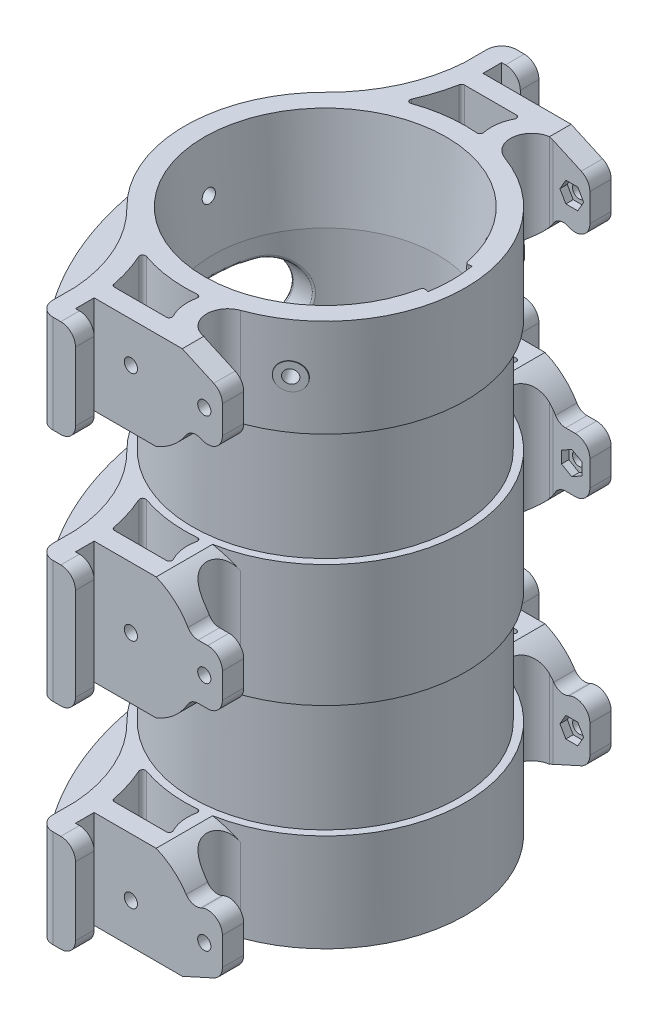
SolidWorks part; units mm, degrees
ref_plane "Front Plane" through (0, 0, 0) normal (0, 0, 1) x (1, 0, 0)
ref_plane "Top Plane" through (0, 0, 0) normal (0, 1, 0) x (1, 0, 0)
ref_plane "Right Plane" through (0, 0, 0) normal (1, 0, 0) x (0, 0, -1)
sketch "Sketch1" plane through (0, 0, 0) normal (0, 1, 0) x (1, 0, 0)
  line L0 (0, 38.25) -> (0, 45.25) construction
  circle A0 centre (0, 0) radius 38.25
  circle A1 centre (0, 0) radius 45.25
  dimension "D1" = 76.5
  dimension "D2" = 7
extrude "Boss-Extrude1" add sketch "Sketch1" along normal mid plane 185
sketch "Sketch2" plane through (0, -92.5, 0) normal (0, -1, 0) x (1, 0, 0)
  line L0 (0, 36.25) -> (0, 38.25) construction
  circle A0 centre (0, 0) radius 36.25
  circle A1 centre (0, 0) radius 38.25 construction
  circle A2 centre (0, 0) radius 38.25
  dimension "D1" = 2
extrude "Boss-Extrude2" add sketch "Sketch2" against normal blind 100 from offset 6.35 offset against normal yes
sketch "Sketch7" plane through (0, 0, 0) normal (1, 0, 0) x (0, 0, -1)
  line L0 (45.25, 92.5) -> (-45.25, 92.5) construction
  line L1 (12.5, 40) -> (-12.5, 40) construction
  line L2 (12.5, 27.5) -> (-12.5, 27.5)
  line L3 (12.5, 52.5) -> (-12.5, 52.5)
  circle A0 centre (0, 40) radius 12.5 construction
  arc A1 (12.5, 27.5) -> (12.5, 52.5) centre (12.5, 40) ccw
  arc A2 (-12.5, 52.5) -> (-12.5, 27.5) centre (-12.5, 40) ccw
  point P7 (0, 40)
  dimension "D2" = 25
  dimension "D3" = 25
  dimension "D1" = 52.5
extrude "Cut-Extrude4" cut sketch "Sketch7" against normal through all
sketch "Sketch8" plane through (0, 0, 0) normal (0, 1, 0) x (1, 0, 0)
  line L1 (17.5, -66.175) -> (128.1882, -66.175) construction
  line L2 (-18.85, -66.175) -> (-18.85, -78.875)
  line L3 (-18.85, -78.875) -> (-6.15, -78.875)
  line L4 (45.25, 0) -> (-45.25, 0) construction
  line L5 (31.75, 0) -> (50, 0) construction
  line L6 (-6.15, -78.875) -> (-6.15, -72.525)
  line L7 (-12.5, -72.525) -> (17.5, -72.525) construction
  line L8 (-6.15, -72.525) -> (-12.5, -72.525)
  line L9 (-12.5, -72.525) -> (-12.5, -66.175)
  line L10 (-12.5, -66.175) -> (43.65, -66.175)
  line L11 (-12.5, 66.175) -> (43.65, 66.175)
  line L12 (-12.5, 72.525) -> (-12.5, 66.175)
  line L13 (-6.15, 72.525) -> (-12.5, 72.525)
  line L14 (-6.15, 78.875) -> (-6.15, 72.525)
  line L15 (-18.85, 78.875) -> (-6.15, 78.875)
  line L16 (-18.85, 66.175) -> (-18.85, 78.875)
  line L18 (43.65, -66.175) -> (43.65, -58.9107)
  line L19 (43.65, -58.9107) -> (18.65, -58.9107)
  line L20 (43.65, 58.9107) -> (18.65, 58.9107)
  line L21 (43.65, 66.175) -> (43.65, 58.9107)
  line L22 (-12.5, -72.525) -> (-18.85, -72.525) construction
  arc A0 (-32.8241, -31.1471) -> (-18.85, -66.175) centre (-69.7381, -66.175) cw
  circle A1 centre (0, 0) radius 45.25 construction
  arc A2 (-32.8241, -31.1471) -> (15.7007, -42.4388) centre (0, 0) ccw
  arc A3 (-32.8241, 31.1471) -> (15.7007, 42.4388) centre (0, 0) cw
  arc A4 (-32.8241, 31.1471) -> (-18.85, 66.175) centre (-69.7381, 66.175) ccw
  arc A9 (18.65, -58.9107) -> (15.7007, -42.4388) centre (18.65, -50.4107) cw
  arc A10 (18.65, 58.9107) -> (15.7007, 42.4388) centre (18.65, 50.4107) ccw
  dimension "D1" = 8.5
  dimension "D2" = 62.5
  dimension "D3" = 25
extrude "Boss-Extrude3" add sketch "Sketch8" along normal up to surface and the other way up to surface up to face at (0, 92.5, 45.25) other way up to face at (0, -92.5, 45.25)
sketch "Sketch10" plane through (0, 0, 66.175) normal (0, 0, 1) x (1, 0, 0)
  line L0 (17.5, -92.5) -> (43.65, -92.5)
  line L1 (43.65, -92.5) -> (43.65, -80.6536)
  line L2 (-6.15, -59.2129) -> (-32.8241, -59.2129)
  line L3 (128.1882, -42.3564) -> (17.5, -92.5) construction
  line L4 (43.65, -80.6536) -> (17.5, -92.5)
  line L5 (43.65, 80.6536) -> (43.65, 92.5)
  line L6 (17.5, 92.5) -> (128.1882, 42.3564) construction
  line L7 (43.65, 92.5) -> (17.5, 92.5)
  line L8 (-12.5, 92.5) -> (43.65, 92.5) construction
  line L9 (17.5, 92.5) -> (43.65, 80.6536)
  line L10 (43.65, -60.1882) -> (43.65, -9.3209)
  line L11 (79.953, -43.7423) -> (23.8431, -69.161) construction
  line L12 (22.9086, -9.3209) -> (60.2886, -9.3209) construction
  line L21 (22.9086, -9.3209) -> (43.65, -9.3209)
  line L23 (43.65, -60.1882) -> (23.8431, -69.161)
  line L25 (-6.15, 92.5) -> (-6.15, -92.5) construction
  line L26 (-32.8241, 92.5) -> (-32.8241, -92.5) construction
  line L32 (-32.8241, -59.2129) -> (-32.8241, -20.7871)
  line L36 (-32.8241, -20.7871) -> (-6.15, -20.7871)
  line L40 (0, 0) -> (-32.8241, 0) construction
  line L45 (8.611, -59.2129) -> (-6.15, -59.2129)
  line L46 (8.611, -20.7871) -> (-6.15, -20.7871)
  line L47 (-32.8241, 59.2129) -> (-32.8241, 20.7871)
  line L48 (-6.15, 59.2129) -> (-32.8241, 59.2129)
  line L49 (8.611, 59.2129) -> (-6.15, 59.2129)
  line L50 (43.65, 60.1882) -> (23.8431, 69.161)
  line L51 (43.65, 60.1882) -> (43.65, 9.3209)
  line L52 (22.9086, 9.3209) -> (43.65, 9.3209)
  line L53 (8.611, 20.7871) -> (-6.15, 20.7871)
  line L54 (-32.8241, 20.7871) -> (-6.15, 20.7871)
  line L55 (43.65, 92.5) -> (43.65, -92.5) construction
  arc A6 (18.8427, -67.7035) -> (23.8431, -69.161) centre (22.1925, -65.5175) ccw construction
  arc A7 (18.8427, -67.7035) -> (8.611, -59.2129) centre (0, -80) ccw construction
  arc A10 (8.611, -20.7871) -> (19.4507, -11.3102) centre (0, 0) ccw construction
  arc A11 (22.9086, -9.3209) -> (19.4507, -11.3102) centre (22.9086, -13.3209) ccw construction
  arc A18 (18.8427, -67.7035) -> (23.8431, -69.161) centre (22.1925, -65.5175) ccw
  arc A19 (18.8427, -67.7035) -> (8.611, -59.2129) centre (0, -80) ccw
  arc A22 (8.611, -20.7871) -> (19.4507, -11.3102) centre (0, 0) ccw
  arc A23 (22.9086, -9.3209) -> (19.4507, -11.3102) centre (22.9086, -13.3209) ccw
  arc A24 (18.8427, 67.7035) -> (8.611, 59.2129) centre (0, 80) cw
  arc A25 (18.8427, 67.7035) -> (23.8431, 69.161) centre (22.1925, 65.5175) cw
  arc A26 (22.9086, 9.3209) -> (19.4507, 11.3102) centre (22.9086, 13.3209) cw
  arc A27 (8.611, 20.7871) -> (19.4507, 11.3102) centre (0, 0) cw
extrude "Cut-Extrude6" cut sketch "Sketch10" against normal up to surface and the other way through all up to face at (-41.5057, 40, 0)
sketch "Sketch11" plane through (0, 0, -78.875) normal (0, 0, -1) x (-1, 0, 0)
  line L3 (-43.65, 92.5) -> (-43.65, 80.6536)
  line L4 (-17.5, 92.5) -> (-43.65, 92.5)
  line L5 (-43.65, 80.6536) -> (-17.5, 92.5)
  line L6 (-43.65, 92.5) -> (-43.65, 80.6536)
  line L7 (-17.5, 92.5) -> (-43.65, 92.5)
  line L8 (-43.65, 80.6536) -> (-17.5, 92.5)
  line L9 (-43.65, -92.5) -> (-17.5, -92.5)
  line L10 (-43.65, -80.6536) -> (-43.65, -92.5)
  line L11 (-17.5, -92.5) -> (-43.65, -80.6536)
  line L12 (-43.65, -92.5) -> (-17.5, -92.5)
  line L13 (-43.65, -80.6536) -> (-43.65, -92.5)
  line L14 (-17.5, -92.5) -> (-43.65, -80.6536)
  line L20 (32.8241, 20.7871) -> (32.8241, 59.2129)
  line L21 (6.15, 20.7871) -> (32.8241, 20.7871)
  line L22 (-8.611, 20.7871) -> (6.15, 20.7871)
  line L23 (-43.65, 9.3209) -> (-22.9086, 9.3209)
  line L24 (-43.65, 60.1882) -> (-43.65, 9.3209)
  line L25 (-23.8431, 69.161) -> (-43.65, 60.1882)
  line L26 (6.15, 59.2129) -> (-8.611, 59.2129)
  line L27 (32.8241, 59.2129) -> (6.15, 59.2129)
  line L28 (32.8241, 20.7871) -> (32.8241, 59.2129)
  line L29 (6.15, 20.7871) -> (32.8241, 20.7871)
  line L30 (-8.611, 20.7871) -> (6.15, 20.7871)
  line L31 (-43.65, 9.3209) -> (-22.9086, 9.3209)
  line L32 (-43.65, 60.1882) -> (-43.65, 9.3209)
  line L33 (-23.8431, 69.161) -> (-43.65, 60.1882)
  line L34 (6.15, 59.2129) -> (-8.611, 59.2129)
  line L35 (32.8241, 59.2129) -> (6.15, 59.2129)
  line L36 (-22.9086, -9.3209) -> (-43.65, -9.3209)
  line L37 (-43.65, -9.3209) -> (-43.65, -60.1882)
  line L38 (-43.65, -60.1882) -> (-23.8431, -69.161)
  line L39 (-8.611, -59.2129) -> (6.15, -59.2129)
  line L40 (6.15, -59.2129) -> (32.8241, -59.2129)
  line L41 (32.8241, -59.2129) -> (32.8241, -20.7871)
  line L42 (32.8241, -20.7871) -> (6.15, -20.7871)
  line L43 (6.15, -20.7871) -> (-8.611, -20.7871)
  line L44 (-22.9086, -9.3209) -> (-43.65, -9.3209)
  line L45 (-43.65, -9.3209) -> (-43.65, -60.1882)
  line L46 (-43.65, -60.1882) -> (-23.8431, -69.161)
  line L47 (-8.611, -59.2129) -> (6.15, -59.2129)
  line L48 (6.15, -59.2129) -> (32.8241, -59.2129)
  line L49 (32.8241, -59.2129) -> (32.8241, -20.7871)
  line L50 (32.8241, -20.7871) -> (6.15, -20.7871)
  line L51 (6.15, -20.7871) -> (-8.611, -20.7871)
  arc A4 (-8.611, 20.7871) -> (-19.4507, 11.3102) centre (0, 0) ccw
  arc A5 (-22.9086, 9.3209) -> (-19.4507, 11.3102) centre (-22.9086, 13.3209) ccw
  arc A6 (-18.8427, 67.7035) -> (-23.8431, 69.161) centre (-22.1925, 65.5175) ccw
  arc A7 (-18.8427, 67.7035) -> (-8.611, 59.2129) centre (0, 80) ccw
  arc A8 (-8.611, 20.7871) -> (-19.4507, 11.3102) centre (0, 0) ccw
  arc A9 (-22.9086, 9.3209) -> (-19.4507, 11.3102) centre (-22.9086, 13.3209) ccw
  arc A10 (-18.8427, 67.7035) -> (-23.8431, 69.161) centre (-22.1925, 65.5175) ccw
  arc A11 (-18.8427, 67.7035) -> (-8.611, 59.2129) centre (0, 80) ccw
  arc A12 (-23.8431, -69.161) -> (-18.8427, -67.7035) centre (-22.1925, -65.5175) ccw
  arc A13 (-8.611, -59.2129) -> (-18.8427, -67.7035) centre (0, -80) ccw
  arc A14 (-19.4507, -11.3102) -> (-8.611, -20.7871) centre (0, 0) ccw
  arc A15 (-19.4507, -11.3102) -> (-22.9086, -9.3209) centre (-22.9086, -13.3209) ccw
  arc A16 (-23.8431, -69.161) -> (-18.8427, -67.7035) centre (-22.1925, -65.5175) ccw
  arc A17 (-8.611, -59.2129) -> (-18.8427, -67.7035) centre (0, -80) ccw
  arc A18 (-19.4507, -11.3102) -> (-8.611, -20.7871) centre (0, 0) ccw
  arc A19 (-19.4507, -11.3102) -> (-22.9086, -9.3209) centre (-22.9086, -13.3209) ccw
  dimension "D1" = 0
  dimension "D2" = 0
  dimension "D3" = 0
  dimension "D4" = 0
extrude "Cut-Extrude7" cut sketch "Sketch11" against normal up to surface (66.9486 mm away) up to face at (-3.9052, 0.3336, 17.6166)
fillet "Fillet5" radius 5 6 edges at (-18.85, -75.8565, -78.875) (-18.85, 0, -78.875) (-18.85, 75.8565, -78.875) (-18.85, 0, 78.875) (-18.85, -75.8565, 78.875) (-18.85, 75.8565, 78.875)
sketch "Sketch14" plane through (0, 0, -66.175) normal (0, 0, -1) x (-1, 0, 0)
  line L0 (0, 0) -> (-25, 0) construction
  line L5 (-25, 78.8696) -> (-25, 0) construction
  circle A3 centre (-25, 78.8696) radius 2.25
  circle A5 centre (-25, 0) radius 2.25
  circle A7 centre (-25, -78.8696) radius 2.25
  circle A8 centre (0, 0) radius 2.25
  circle A9 centre (0, 78.8696) radius 2.25
  circle A10 centre (0, -78.8696) radius 2.25
  dimension "D1" = 25
  dimension "D2" = 78.8696
  dimension "D3" = 4.5
extrude "Cut-Extrude8" cut sketch "Sketch14" against normal up to surface (7.2643 mm away) up to face at (27.8361, -73.0039, -58.9107)
sketch "Sketch15" plane through (0, 0, 66.175) normal (0, 0, 1) x (1, 0, 0)
  circle A1 centre (0, -78.8696) radius 2.25
  circle A3 centre (0, -78.8696) radius 2.25
  circle A5 centre (0, 78.8696) radius 2.25
  circle A7 centre (0, 78.8696) radius 2.25
  circle A9 centre (0, 0) radius 2.25
  circle A11 centre (0, 0) radius 2.25
  circle A13 centre (25, 78.8696) radius 2.25
  circle A14 centre (25, 78.8696) radius 2.25
  circle A15 centre (25, -78.8696) radius 2.25
  circle A16 centre (25, -78.8696) radius 2.25
  circle A17 centre (25, 0) radius 2.25
  circle A18 centre (25, 0) radius 2.25
  dimension "D1" = 0
  dimension "D2" = 0
  dimension "D3" = 0
  dimension "D4" = 0
  dimension "D5" = 0
  dimension "D6" = 0
extrude "Cut-Extrude9" cut sketch "Sketch15" against normal up to surface (7.2643 mm away) up to face at (27.8361, -73.0039, 58.9107)
sketch "Sketch16" plane through (0, 92.5, 0) normal (0, 1, 0) x (1, 0, 0)
  line L0 (-45.25, 0) -> (-47.75, 0) construction
  circle A0 centre (0, 0) radius 47.75
  circle A1 centre (0, 0) radius 45.25
  arc A2 (-32.8241, 31.1471) -> (-32.8241, -31.1471) centre (0, 0) ccw construction
  dimension "D1" = 2.5
extrude "Boss-Extrude4" add sketch "Sketch16" against normal up to surface (33.2871 mm away) up to face at (-10.3824, 59.2129, 65.577)
sketch "Sketch17" plane through (0, -92.5, 0) normal (0, -1, 0) x (1, 0, 0)
  circle A1 centre (0, 0) radius 45.25
  circle A2 centre (0, 0) radius 45.25
  circle A3 centre (0, 0) radius 47.75
  circle A4 centre (0, 0) radius 47.75
  dimension "D1" = 0
  dimension "D2" = 0
extrude "Boss-Extrude5" add sketch "Sketch17" against normal up to surface (33.2871 mm away) up to face at (-10.3824, -59.2129, 65.577)
sketch "Sketch18" plane through (0, -20.7871, 0) normal (0, -1, 0) x (1, 0, 0)
  circle A1 centre (0, 0) radius 47.75
  circle A2 centre (0, 0) radius 47.75
  circle A3 centre (0, 0) radius 45.25
  circle A4 centre (0, 0) radius 45.25
  dimension "D1" = 0
  dimension "D2" = 0
extrude "Boss-Extrude6" add sketch "Sketch18" against normal up to surface (41.5741 mm away) up to face at (-10.3824, 20.7871, 65.577)
sketch "Sketch20" plane through (0, 0, 0) normal (1, 0, 0) x (0, 0, -1)
  line L0 (-45.25, -20.7871) -> (45.25, -20.7871) construction
  line L1 (46.9672, -59.2129) -> (-46.9672, -59.2129) construction
  line L2 (-45.25, 59.2129) -> (45.25, 59.2129) construction
  line L3 (46.9672, 20.7871) -> (-46.9672, 20.7871) construction
  line L4 (-45.25, -20.7871) -> (45.25, -20.7871) construction
  line L5 (46.9672, -59.2129) -> (-46.9672, -59.2129) construction
  line L6 (-45.25, 59.2129) -> (45.25, 59.2129) construction
  line L7 (46.9672, 20.7871) -> (-46.9672, 20.7871) construction
  line L8 (0, -20.7871) -> (0, -59.2129) construction
  line L9 (0, 59.2129) -> (0, 20.7871) construction
  line L10 (-10, 40) -> (10, 40) construction
  line L11 (-10, 45) -> (10, 45)
  line L12 (-10, 35) -> (10, 35)
  line L13 (0, 0) -> (46.4328, 0) construction
  line L14 (46.4328, 19.5496) -> (46.4328, -19.5496) construction
  line L15 (-10, -40) -> (10, -40) construction
  line L16 (-10, -45) -> (10, -45)
  line L17 (-10, -35) -> (10, -35)
  arc A2 (-10, 45) -> (-10, 35) centre (-10, 40) ccw
  arc A3 (10, 35) -> (10, 45) centre (10, 40) ccw
  arc A4 (-10, -45) -> (-10, -35) centre (-10, -40) cw
  arc A5 (10, -35) -> (10, -45) centre (10, -40) cw
  point P2 (0, 40)
  point P14 (0, -20.7871)
  point P30 (0, -40)
  dimension "D1" = 20
  dimension "D2" = 5
extrude "Cut-Extrude10" [suppressed] cut sketch "Sketch20" along normal through all
pattern_circular "CirPattern1" [suppressed] count 6 over 360 reverse direction yes of bodies 118
ref_plane "Plane1" through (-26.1107, -92.5, 39.9787) normal (0, -1, 0) x (-1, 0, 0)
sketch "Sketch23" plane through (0, -92.5, 0) normal (0, -1, 0) x (1, 0, 0)
  line L0 (0, 0) -> (-47.75, 0) construction
  arc A0 (-18.85, 66.175) -> (-33.5786, 33.9491) centre (-68.7395, 69.4978) cw
  arc A1 (-26.1107, 39.9787) -> (-26.1107, -39.9787) centre (0, 0) ccw construction
  arc A2 (-33.5786, 33.9491) -> (-26.1107, 39.9787) centre (0, 0) cw
  arc A3 (-18.85, 66.175) -> (-26.1107, 39.9787) centre (-69.7381, 66.175) cw
  arc A4 (-18.85, -66.175) -> (-26.1107, -39.9787) centre (-69.7381, -66.175) ccw
  arc A5 (-33.5786, -33.9491) -> (-26.1107, -39.9787) centre (0, 0) ccw
  arc A6 (-18.85, -66.175) -> (-33.5786, -33.9491) centre (-68.7395, -69.4978) ccw
  arc A7 (-26.1107, 39.9787) -> (-18.85, 66.175) centre (-69.7381, 66.175) ccw construction
  dimension "D1" = 50
extrude "Boss-Extrude7" add sketch "Sketch23" against normal up to surface (33.2871 mm away) up to face at (-8.8243, -59.2129, 0)
sketch "Sketch24" plane through (0, 92.5, 0) normal (0, 1, 0) x (1, 0, 0)
  arc A3 (-26.1107, 39.9787) -> (-18.85, 66.175) centre (-69.7381, 66.175) ccw
  arc A4 (-26.1107, 39.9787) -> (-33.5786, 33.9491) centre (0, 0) ccw
  arc A5 (-33.5786, 33.9491) -> (-18.85, 66.175) centre (-68.7395, 69.4978) ccw
  arc A6 (-26.1107, 39.9787) -> (-18.85, 66.175) centre (-69.7381, 66.175) ccw
  arc A7 (-26.1107, 39.9787) -> (-33.5786, 33.9491) centre (0, 0) ccw
  arc A8 (-33.5786, 33.9491) -> (-18.85, 66.175) centre (-68.7395, 69.4978) ccw
  arc A9 (-18.85, -66.175) -> (-33.5786, -33.9491) centre (-68.7395, -69.4978) ccw
  arc A10 (-33.5786, -33.9491) -> (-26.1107, -39.9787) centre (0, 0) ccw
  arc A11 (-18.85, -66.175) -> (-26.1107, -39.9787) centre (-69.7381, -66.175) ccw
  arc A12 (-18.85, -66.175) -> (-33.5786, -33.9491) centre (-68.7395, -69.4978) ccw
  arc A13 (-33.5786, -33.9491) -> (-26.1107, -39.9787) centre (0, 0) ccw
  arc A14 (-18.85, -66.175) -> (-26.1107, -39.9787) centre (-69.7381, -66.175) ccw
  dimension "D1" = 0
  dimension "D2" = 0
extrude "Boss-Extrude8" add sketch "Sketch24" against normal up to surface (33.2871 mm away) up to face at (-45.25, 59.2129, 0)
sketch "Sketch25" plane through (0, 20.7871, 0) normal (0, 1, 0) x (1, 0, 0)
  arc A3 (-18.85, -66.175) -> (-33.5786, -33.9491) centre (-68.7395, -69.4978) ccw
  arc A4 (-33.5786, -33.9491) -> (-26.1107, -39.9787) centre (0, 0) ccw
  arc A5 (-18.85, -66.175) -> (-26.1107, -39.9787) centre (-69.7381, -66.175) ccw
  arc A6 (-18.85, -66.175) -> (-33.5786, -33.9491) centre (-68.7395, -69.4978) ccw
  arc A7 (-33.5786, -33.9491) -> (-26.1107, -39.9787) centre (0, 0) ccw
  arc A8 (-18.85, -66.175) -> (-26.1107, -39.9787) centre (-69.7381, -66.175) ccw
  arc A9 (-26.1107, 39.9787) -> (-18.85, 66.175) centre (-69.7381, 66.175) ccw
  arc A10 (-33.5786, 33.9491) -> (-18.85, 66.175) centre (-68.7395, 69.4978) ccw
  arc A11 (-26.1107, 39.9787) -> (-33.5786, 33.9491) centre (0, 0) ccw
  arc A12 (-26.1107, 39.9787) -> (-18.85, 66.175) centre (-69.7381, 66.175) ccw
  arc A13 (-33.5786, 33.9491) -> (-18.85, 66.175) centre (-68.7395, 69.4978) ccw
  arc A14 (-26.1107, 39.9787) -> (-33.5786, 33.9491) centre (0, 0) ccw
  dimension "D1" = 0
  dimension "D2" = 0
extrude "Boss-Extrude9" add sketch "Sketch25" against normal up to surface (41.5741 mm away) up to face at (-45.25, -20.7871, 0)
sketch "Sketch27" plane through (0, 0, 0) normal (0, 0, 1) x (1, 0, 0)
  line L0 (38.25, 59.2129) -> (41.1622, 92.5)
  line L3 (38.25, 59.2129) -> (0, 59.2129) construction
  line L5 (-18.85, 92.5) -> (-33.5786, 92.5) construction
  line L6 (38.25, 59.2129) -> (38.25, 92.5)
  line L7 (38.25, 92.5) -> (41.1622, 92.5)
  line L8 (0, 59.2129) -> (0, 92.5) construction
  dimension "D1" = 33.2871
  dimension "D2" = 5
  dimension "D3" = 38.25
  dimension "D4" = 38.25
  dimension "D5" = 38.25
revolve "Cut-Revolve1" cut sketch "Sketch27" angle 360 about L8
sketch "Sketch28" plane through (0, 92.5, 0) normal (0, 1, 0) x (1, 0, 0)
  line L1 (43.65, 58.9107) -> (18.65, 58.9107) construction
  line L2 (0, 0) -> (47.75, 0) construction
  line L3 (11.1383, 46.4328) -> (10.15, 46.6698)
  line L4 (10.15, 46.6698) -> (10.15, 58.8326)
  line L5 (10.15, 58.8326) -> (17.5, 58.8326)
  line L6 (10.15, -58.8326) -> (17.5, -58.8326)
  line L7 (10.15, -46.6698) -> (10.15, -58.8326)
  line L8 (11.1383, -46.4328) -> (10.15, -46.6698)
  arc A0 (17.5, 58.8326) -> (16.1276, 44.944) centre (18.5576, 51.716) ccw
  arc A1 (11.1383, -46.4328) -> (11.1383, 46.4328) centre (0, 0) ccw construction
  arc A2 (16.1276, 44.944) -> (11.1383, 46.4328) centre (0, 0) ccw
  arc A7 (17.5, 58.8326) -> (11.1383, 46.4328) centre (18.65, 50.4107) ccw construction
  arc A8 (16.1276, -44.944) -> (11.1383, -46.4328) centre (0, 0) cw
  arc A9 (17.5, -58.8326) -> (16.1276, -44.944) centre (18.5576, -51.716) cw
extrude "Boss-Extrude13" add sketch "Sketch28" against normal up to surface (26.6421 mm away) up to face at (13.4579, 62.8457, 57.713)
sketch "Sketch29" plane through (0, -92.5, 0) normal (0, -1, 0) x (1, 0, 0)
  line L3 (11.1383, -46.4328) -> (10.15, -46.6698)
  line L4 (10.15, -46.6698) -> (10.15, -58.8326)
  line L5 (10.15, -58.8326) -> (17.5, -58.8326)
  line L6 (11.1383, -46.4328) -> (10.15, -46.6698)
  line L7 (10.15, -46.6698) -> (10.15, -58.8326)
  line L8 (10.15, -58.8326) -> (17.5, -58.8326)
  line L9 (17.5, 58.8326) -> (10.15, 58.8326)
  line L10 (10.15, 46.6698) -> (11.1383, 46.4328)
  line L11 (10.15, 58.8326) -> (10.15, 46.6698)
  line L12 (17.5, 58.8326) -> (10.15, 58.8326)
  line L13 (10.15, 46.6698) -> (11.1383, 46.4328)
  line L14 (10.15, 58.8326) -> (10.15, 46.6698)
  arc A2 (16.1276, -44.944) -> (17.5, -58.8326) centre (18.5576, -51.716) ccw
  arc A3 (11.1383, -46.4328) -> (16.1276, -44.944) centre (0, 0) ccw
  arc A4 (16.1276, -44.944) -> (17.5, -58.8326) centre (18.5576, -51.716) ccw
  arc A5 (11.1383, -46.4328) -> (16.1276, -44.944) centre (0, 0) ccw
  arc A6 (17.5, 58.8326) -> (16.1276, 44.944) centre (18.5576, 51.716) ccw
  arc A7 (16.1276, 44.944) -> (11.1383, 46.4328) centre (0, 0) ccw
  arc A8 (17.5, 58.8326) -> (16.1276, 44.944) centre (18.5576, 51.716) ccw
  arc A9 (16.1276, 44.944) -> (11.1383, 46.4328) centre (0, 0) ccw
  dimension "D1" = 0
  dimension "D2" = 0
extrude "Boss-Extrude14" add sketch "Sketch29" against normal up to surface (32.0496 mm away) up to face at (13.7418, -62.9735, 57.3608)
sketch "Sketch30" plane through (0, 0, 0) normal (0, 1, 0) x (1, 0, 0)
  line L3 (10.15, 46.6698) -> (11.1383, 46.4328)
  line L4 (10.15, 58.8326) -> (10.15, 46.6698)
  line L5 (17.5, 58.8326) -> (10.15, 58.8326)
  line L6 (10.15, 46.6698) -> (11.1383, 46.4328)
  line L7 (10.15, 58.8326) -> (10.15, 46.6698)
  line L8 (17.5, 58.8326) -> (10.15, 58.8326)
  line L9 (10.15, -46.6698) -> (10.15, -58.8326)
  line L10 (10.15, -58.8326) -> (17.5, -58.8326)
  line L11 (11.1383, -46.4328) -> (10.15, -46.6698)
  line L12 (10.15, -46.6698) -> (10.15, -58.8326)
  line L13 (10.15, -58.8326) -> (17.5, -58.8326)
  line L14 (11.1383, -46.4328) -> (10.15, -46.6698)
  arc A2 (17.5, 58.8326) -> (16.1276, 44.944) centre (18.5576, 51.716) ccw
  arc A3 (16.1276, 44.944) -> (11.1383, 46.4328) centre (0, 0) ccw
  arc A4 (17.5, 58.8326) -> (16.1276, 44.944) centre (18.5576, 51.716) ccw
  arc A5 (16.1276, 44.944) -> (11.1383, 46.4328) centre (0, 0) ccw
  arc A6 (16.1276, -44.944) -> (17.5, -58.8326) centre (18.5576, -51.716) ccw
  arc A7 (11.1383, -46.4328) -> (16.1276, -44.944) centre (0, 0) ccw
  arc A8 (16.1276, -44.944) -> (17.5, -58.8326) centre (18.5576, -51.716) ccw
  arc A9 (11.1383, -46.4328) -> (16.1276, -44.944) centre (0, 0) ccw
  dimension "D1" = 0
  dimension "D2" = 0
extrude "Boss-Extrude15" add sketch "Sketch30" against normal up to surface and the other way up to surface up to face at (13.9691, -16.7184, -57.3608) other way up to face at (13.6851, 16.8462, -57.713)
ref_plane "Plane2" through (0, 75.8565, 0) normal (0, 1, 0) x (1, 0, 0)
sketch "Sketch31" plane through (0, 75.8565, 0) normal (0, 1, 0) x (1, 0, 0)
  line L0 (0, 0) -> (27.3883, 39.1145) construction
  line L1 (0, 0) -> (-47.75, 0) construction
  arc A0 (16.1276, -44.944) -> (16.1276, 44.944) centre (0, 0) ccw construction
  arc A1 (-33.5786, 33.9491) -> (-33.5786, -33.9491) centre (0, 0) ccw construction
  dimension "D1" = 125
ref_plane "Plane3" through (27.3883, 75.8565, -39.1145) normal (0.5736, 0, -0.8192) x (-0.8192, 0, -0.5736)
sketch "Sketch34" plane through (0, 75.8565, 0) normal (0, 1, 0) x (1, 0, 0)
  line L2 (0, 0) -> (-47.76, 0) construction
  line L5 (-18.85, 73.875) -> (-18.85, 66.175) construction
  line L6 (-18.85, 73.875) -> (-18.85, 66.175)
  line L7 (-18.85, -73.875) -> (-18.85, -66.175)
  arc A1 (-17.5219, 77.2686) -> (-17.5219, -77.2686) centre (66.083, 0) ccw
  arc A9 (-13.85, 78.875) -> (-18.85, 73.875) centre (-13.85, 73.875) ccw construction
  arc A17 (-18.85, -73.875) -> (-13.85, -78.875) centre (-13.85, -73.875) ccw construction
  arc A18 (-17.5219, 77.2686) -> (-18.85, 73.875) centre (-13.85, 73.875) ccw
  arc A19 (-33.5786, 33.9491) -> (-33.5786, -33.9491) centre (0, 0) ccw construction
  arc A20 (-33.5786, 33.9491) -> (-18.85, 66.175) centre (-68.7395, 69.4978) ccw construction
  arc A21 (-33.5786, 33.9491) -> (-33.5786, -33.9491) centre (0, 0) ccw
  arc A22 (-33.5786, 33.9491) -> (-18.85, 66.175) centre (-68.7395, 69.4978) ccw
  arc A23 (-33.5786, -33.9491) -> (-18.85, -66.175) centre (-68.7395, -69.4978) cw
  arc A24 (-17.5219, -77.2686) -> (-18.85, -73.875) centre (-13.85, -73.875) cw
  point P24 (-47.75, 0)
  dimension "D1" = 0.01
extrude "Boss-Extrude17" add sketch "Sketch34" along normal mid plane 15
ref_plane "Plane4" through (0, 0, 0) normal (0, -1, 0) x (-1, 0, 0)
ref_plane "Plane5" through (0, -75.8565, 0) normal (0, -1, 0) x (-1, 0, 0)
sketch "Sketch35" plane through (0, 0, 0) normal (0, -1, 0) x (-1, 0, 0)
  line L3 (18.85, -66.175) -> (18.85, -73.875)
  line L5 (18.85, 73.875) -> (18.85, 66.175)
  line L6 (18.85, -66.175) -> (18.85, -73.875)
  line L7 (18.85, 73.875) -> (18.85, 66.175)
  arc A12 (18.85, 66.175) -> (33.5786, 33.9491) centre (68.7395, 69.4978) ccw
  arc A13 (33.5786, -33.9491) -> (33.5786, 33.9491) centre (0, 0) ccw
  arc A20 (33.5786, -33.9491) -> (18.85, -66.175) centre (68.7395, -69.4978) ccw
  arc A21 (17.5219, -77.2686) -> (18.85, -73.875) centre (13.85, -73.875) ccw
  arc A25 (17.5219, -77.2686) -> (17.5219, 77.2686) centre (-66.083, 0) ccw
  arc A38 (18.85, 73.875) -> (17.5219, 77.2686) centre (13.85, 73.875) ccw
  arc A39 (18.85, 66.175) -> (33.5786, 33.9491) centre (68.7395, 69.4978) ccw
  arc A40 (33.5786, -33.9491) -> (33.5786, 33.9491) centre (0, 0) ccw
  arc A41 (33.5786, -33.9491) -> (18.85, -66.175) centre (68.7395, -69.4978) ccw
  arc A42 (17.5219, -77.2686) -> (18.85, -73.875) centre (13.85, -73.875) ccw
  arc A43 (17.5219, -77.2686) -> (17.5219, 77.2686) centre (-66.083, 0) ccw
  arc A44 (18.85, 73.875) -> (17.5219, 77.2686) centre (13.85, 73.875) ccw
  dimension "D1" = 0
extrude "Boss-Extrude18" add sketch "Sketch35" along normal mid plane 19.1435
sketch "Sketch36" plane through (0, -75.8565, 0) normal (0, -1, 0) x (-1, 0, 0)
  line L3 (18.85, 73.875) -> (18.85, 66.175)
  line L5 (18.85, -66.175) -> (18.85, -73.875)
  line L6 (18.85, 73.875) -> (18.85, 66.175)
  line L7 (18.85, -66.175) -> (18.85, -73.875)
  arc A12 (18.85, 66.175) -> (33.5786, 33.9491) centre (68.7395, 69.4978) ccw
  arc A13 (33.5786, -33.9491) -> (33.5786, 33.9491) centre (0, 0) ccw
  arc A20 (33.5786, -33.9491) -> (18.85, -66.175) centre (68.7395, -69.4978) ccw
  arc A21 (17.5219, -77.2686) -> (18.85, -73.875) centre (13.85, -73.875) ccw
  arc A25 (17.5219, -77.2686) -> (17.5219, 77.2686) centre (-66.083, 0) ccw
  arc A38 (18.85, 73.875) -> (17.5219, 77.2686) centre (13.85, 73.875) ccw
  arc A39 (18.85, 66.175) -> (33.5786, 33.9491) centre (68.7395, 69.4978) ccw
  arc A40 (33.5786, -33.9491) -> (33.5786, 33.9491) centre (0, 0) ccw
  arc A41 (33.5786, -33.9491) -> (18.85, -66.175) centre (68.7395, -69.4978) ccw
  arc A42 (17.5219, -77.2686) -> (18.85, -73.875) centre (13.85, -73.875) ccw
  arc A43 (17.5219, -77.2686) -> (17.5219, 77.2686) centre (-66.083, 0) ccw
  arc A44 (18.85, 73.875) -> (17.5219, 77.2686) centre (13.85, 73.875) ccw
  dimension "D1" = 0
extrude "Boss-Extrude19" add sketch "Sketch36" along normal mid plane 15
sketch "Sketch32" plane through (27.3883, 75.8565, -39.1145) normal (0.5736, 0, -0.8192) x (-0.8192, 0, -0.5736)
  circle A0 centre (0, 0) radius 4.5
  dimension "D1" = 9
extrude "Boss-Extrude16" add sketch "Sketch32" against normal blind 1 and the other way blind 0.2
sketch "Sketch33" plane through (27.503, 0, -39.2783) normal (0.5736, 0, -0.8192) x (-0.8192, 0, -0.5736)
  circle A0 centre (0, 75.8565) radius 2.25
  dimension "D1" = 4.5
extrude "Cut-Extrude11" cut sketch "Sketch33" against normal up to surface (8.3077 mm away) up to face at (0, 92.5, -41.1622)
pattern_circular "CirPattern2" count 3 every 125 about axis through (0, -75.8444, 0) along (0, 1, 0) of "Boss-Extrude16", "Cut-Extrude11"
sketch "Sketch37" plane through (0, 0, 58.9107) normal (0, 0, -1) x (-1, 0, 0)
  line L1 (-2.0207, -3.5) -> (2.0207, -3.5)
  line L2 (2.0207, -3.5) -> (4.0415, 0)
  line L3 (4.0415, 0) -> (2.0207, 3.5)
  line L4 (2.0207, 3.5) -> (-2.0207, 3.5)
  line L5 (-2.0207, 3.5) -> (-4.0415, 0)
  line L6 (-4.0415, 0) -> (-2.0207, -3.5)
  line L13 (-28.5, 2.0207) -> (-28.5, -2.0207)
  line L14 (-28.5, -2.0207) -> (-25, -4.0415)
  line L15 (-25, -4.0415) -> (-21.5, -2.0207)
  line L16 (-21.5, -2.0207) -> (-21.5, 2.0207)
  line L17 (-21.5, 2.0207) -> (-25, 4.0415)
  line L18 (-25, 4.0415) -> (-28.5, 2.0207)
  line L25 (-29.0415, -78.8696) -> (-27.0207, -82.3696)
  line L26 (-27.0207, -82.3696) -> (-22.9793, -82.3696)
  line L27 (-22.9793, -82.3696) -> (-20.9585, -78.8696)
  line L28 (-20.9585, -78.8696) -> (-22.9793, -75.3696)
  line L29 (-22.9793, -75.3696) -> (-27.0207, -75.3696)
  line L30 (-27.0207, -75.3696) -> (-29.0415, -78.8696)
  line L37 (-2.0207, -82.3696) -> (2.0207, -82.3696)
  line L38 (2.0207, -82.3696) -> (4.0415, -78.8696)
  line L39 (4.0415, -78.8696) -> (2.0207, -75.3696)
  line L40 (2.0207, -75.3696) -> (-2.0207, -75.3696)
  line L41 (-2.0207, -75.3696) -> (-4.0415, -78.8696)
  line L42 (-4.0415, -78.8696) -> (-2.0207, -82.3696)
  line L43 (-2.0207, 75.3696) -> (2.0207, 75.3696)
  line L44 (2.0207, 75.3696) -> (4.0415, 78.8696)
  line L45 (4.0415, 78.8696) -> (2.0207, 82.3696)
  line L46 (2.0207, 82.3696) -> (-2.0207, 82.3696)
  line L47 (-2.0207, 82.3696) -> (-4.0415, 78.8696)
  line L48 (-4.0415, 78.8696) -> (-2.0207, 75.3696)
  line L49 (-27.0207, 75.3696) -> (-22.9793, 75.3696)
  line L50 (-22.9793, 75.3696) -> (-20.9585, 78.8696)
  line L51 (-20.9585, 78.8696) -> (-22.9793, 82.3696)
  line L52 (-22.9793, 82.3696) -> (-27.0207, 82.3696)
  line L53 (-27.0207, 82.3696) -> (-29.0415, 78.8696)
  line L54 (-29.0415, 78.8696) -> (-27.0207, 75.3696)
  circle A1 centre (-25, -78.8696) radius 2.25 construction
  circle A3 centre (-25, 0) radius 2.25 construction
  circle A5 centre (0, 0) radius 2.25 construction
  circle A7 centre (-25, -78.8696) radius 2.25 construction
  circle A9 centre (-25, 0) radius 2.25 construction
  circle A11 centre (0, 0) radius 2.25 construction
  circle A12 centre (0, 0) radius 3.5 construction
  circle A13 centre (0, 78.8696) radius 2.25 construction
  circle A14 centre (-25, 0) radius 3.5 construction
  circle A15 centre (-25, 78.8696) radius 2.25 construction
  circle A16 centre (-25, -78.8696) radius 3.5 construction
  circle A17 centre (0, -78.8696) radius 2.25 construction
  circle A18 centre (0, 78.8696) radius 2.25 construction
  circle A19 centre (-25, 78.8696) radius 2.25 construction
  circle A20 centre (0, -78.8696) radius 2.25 construction
  circle A21 centre (0, -78.8696) radius 3.5 construction
  circle A22 centre (0, 78.8696) radius 3.5 construction
  circle A23 centre (-25, 78.8696) radius 3.5 construction
  dimension "D2" = 7
  dimension "D3" = 4.0415
extrude "Cut-Extrude12" cut sketch "Sketch37" against normal blind 2.5
sketch "Sketch39" plane through (0, 0, -58.9107) normal (0, 0, 1) x (1, 0, 0)
  line L78 (-2.0207, -82.3696) -> (2.0207, -82.3696)
  line L79 (-4.0415, -78.8696) -> (-2.0207, -82.3696)
  line L80 (-2.0207, -75.3696) -> (-4.0415, -78.8696)
  line L81 (2.0207, -75.3696) -> (-2.0207, -75.3696)
  line L82 (4.0415, -78.8696) -> (2.0207, -75.3696)
  line L83 (2.0207, -82.3696) -> (4.0415, -78.8696)
  line L84 (-2.0207, -82.3696) -> (2.0207, -82.3696)
  line L85 (-4.0415, -78.8696) -> (-2.0207, -82.3696)
  line L86 (-2.0207, -75.3696) -> (-4.0415, -78.8696)
  line L87 (2.0207, -75.3696) -> (-2.0207, -75.3696)
  line L88 (4.0415, -78.8696) -> (2.0207, -75.3696)
  line L89 (2.0207, -82.3696) -> (4.0415, -78.8696)
  line L90 (-2.0207, -3.5) -> (2.0207, -3.5)
  line L91 (-4.0415, 0) -> (-2.0207, -3.5)
  line L92 (-2.0207, 3.5) -> (-4.0415, 0)
  line L93 (2.0207, 3.5) -> (-2.0207, 3.5)
  line L94 (4.0415, 0) -> (2.0207, 3.5)
  line L95 (2.0207, -3.5) -> (4.0415, 0)
  line L96 (-2.0207, -3.5) -> (2.0207, -3.5)
  line L97 (-4.0415, 0) -> (-2.0207, -3.5)
  line L98 (-2.0207, 3.5) -> (-4.0415, 0)
  line L99 (2.0207, 3.5) -> (-2.0207, 3.5)
  line L100 (4.0415, 0) -> (2.0207, 3.5)
  line L101 (2.0207, -3.5) -> (4.0415, 0)
  line L102 (-2.0207, 75.3696) -> (2.0207, 75.3696)
  line L103 (-4.0415, 78.8696) -> (-2.0207, 75.3696)
  line L104 (-2.0207, 82.3696) -> (-4.0415, 78.8696)
  line L105 (2.0207, 82.3696) -> (-2.0207, 82.3696)
  line L106 (4.0415, 78.8696) -> (2.0207, 82.3696)
  line L107 (2.0207, 75.3696) -> (4.0415, 78.8696)
  line L108 (-2.0207, 75.3696) -> (2.0207, 75.3696)
  line L109 (-4.0415, 78.8696) -> (-2.0207, 75.3696)
  line L110 (-2.0207, 82.3696) -> (-4.0415, 78.8696)
  line L111 (2.0207, 82.3696) -> (-2.0207, 82.3696)
  line L112 (4.0415, 78.8696) -> (2.0207, 82.3696)
  line L113 (2.0207, 75.3696) -> (4.0415, 78.8696)
  line L114 (28.5, -2.0207) -> (28.5, 2.0207)
  line L115 (25, -4.0415) -> (28.5, -2.0207)
  line L116 (21.5, -2.0207) -> (25, -4.0415)
  line L117 (21.5, 2.0207) -> (21.5, -2.0207)
  line L118 (25, 4.0415) -> (21.5, 2.0207)
  line L119 (28.5, 2.0207) -> (25, 4.0415)
  line L120 (28.5, -2.0207) -> (28.5, 2.0207)
  line L121 (25, -4.0415) -> (28.5, -2.0207)
  line L122 (21.5, -2.0207) -> (25, -4.0415)
  line L123 (21.5, 2.0207) -> (21.5, -2.0207)
  line L124 (25, 4.0415) -> (21.5, 2.0207)
  line L125 (28.5, 2.0207) -> (25, 4.0415)
  line L126 (22.9793, 75.3696) -> (27.0207, 75.3696)
  line L127 (20.9585, 78.8696) -> (22.9793, 75.3696)
  line L128 (22.9793, 82.3696) -> (20.9585, 78.8696)
  line L129 (27.0207, 82.3696) -> (22.9793, 82.3696)
  line L130 (29.0415, 78.8696) -> (27.0207, 82.3696)
  line L131 (27.0207, 75.3696) -> (29.0415, 78.8696)
  line L132 (22.9793, 75.3696) -> (27.0207, 75.3696)
  line L133 (20.9585, 78.8696) -> (22.9793, 75.3696)
  line L134 (22.9793, 82.3696) -> (20.9585, 78.8696)
  line L135 (27.0207, 82.3696) -> (22.9793, 82.3696)
  line L136 (29.0415, 78.8696) -> (27.0207, 82.3696)
  line L137 (27.0207, 75.3696) -> (29.0415, 78.8696)
  line L138 (22.9793, -82.3696) -> (27.0207, -82.3696)
  line L139 (20.9585, -78.8696) -> (22.9793, -82.3696)
  line L140 (22.9793, -75.3696) -> (20.9585, -78.8696)
  line L141 (27.0207, -75.3696) -> (22.9793, -75.3696)
  line L142 (29.0415, -78.8696) -> (27.0207, -75.3696)
  line L143 (27.0207, -82.3696) -> (29.0415, -78.8696)
  line L144 (22.9793, -82.3696) -> (27.0207, -82.3696)
  line L145 (20.9585, -78.8696) -> (22.9793, -82.3696)
  line L146 (22.9793, -75.3696) -> (20.9585, -78.8696)
  line L147 (27.0207, -75.3696) -> (22.9793, -75.3696)
  line L148 (29.0415, -78.8696) -> (27.0207, -75.3696)
  line L149 (27.0207, -82.3696) -> (29.0415, -78.8696)
  dimension "D1" = 0
  dimension "D2" = 0
  dimension "D3" = 0
  dimension "D4" = 0
  dimension "D5" = 0
  dimension "D6" = 0
extrude "Cut-Extrude13" cut sketch "Sketch39" against normal blind 2.5
sketch "Sketch44" plane through (0, 0, 0) normal (0, 0, 1) x (1, 0, 0)
  line L0 (41.1622, 92.5) -> (-41.1622, 92.5) construction
  line L1 (41.1622, 92.5) -> (-41.1622, 92.5) construction
  line L2 (41.1622, 92.5) -> (43.1622, 92.5)
  line L3 (38.25, 59.2129) -> (-38.25, 59.2129) construction
  line L4 (38.25, 59.2129) -> (-38.25, 59.2129) construction
  line L5 (38.25, 59.2129) -> (40.25, 59.2129)
  line L6 (40.25, 59.2129) -> (43.1622, 92.5)
  line L7 (38.25, 59.2129) -> (41.1622, 92.5)
  line L8 (0, 59.2129) -> (0, 92.5) construction
  dimension "D1" = 2
revolve "Cut-Revolve2" cut sketch "Sketch44" angle 10 about L8 other way angle 10
fillet "Fillet6" radius 1 2 edges at (39.1029, 75.8565, -6.8949) (39.1029, 75.8565, 6.8949)
sketch "Sketch45" plane through (0, 92.5, 0) normal (0, 1, 0) x (1, 0, 0)
  line L3 (0, 0) -> (47.75, 0) construction
  line L4 (-12.5, 59.5872) -> (7.2438, 59.5872)
  line L5 (-13.0263, 59.5872) -> (7.2438, 59.5872)
  line L6 (-13.0263, -59.5872) -> (7.2438, -59.5872)
  circle A0 centre (0, 0) radius 47.75 construction
  arc A1 (16.1276, -44.944) -> (16.1276, 44.944) centre (0, 0) ccw construction
  arc A2 (5.456, 47.4373) -> (-18.1353, 44.1721) centre (0, 0) ccw
  arc A3 (-18.1353, -44.1721) -> (-13.0263, -59.5872) centre (-68.7395, -69.4978) cw
  arc A4 (5.456, -47.4373) -> (-18.1353, -44.1721) centre (0, 0) cw
  arc A5 (7.2438, -59.5872) -> (5.456, -47.4373) centre (18.5576, -51.716) cw
  arc A6 (-28.946, 29.2653) -> (-12.2768, 65.7372) centre (-68.7395, 69.4978) ccw
  arc A7 (-18.1353, 44.1721) -> (-13.0263, 59.5872) centre (-68.7395, 69.4978) ccw
  arc A9 (7.2438, 59.5872) -> (13.9025, 38.7434) centre (18.5576, 51.716) ccw
  arc A10 (7.2438, 59.5872) -> (5.456, 47.4373) centre (18.5576, 51.716) ccw
  dimension "D1" = 6.5878
  dimension "D2" = 6.5878
extrude "Cut-Extrude14" cut sketch "Sketch45" against normal through all both and the other way through all
fillet "Fillet7" radius 1 24 edges at (5.456, 75.8565, 47.4373) (5.456, 0, 47.4373) (5.456, -75.8565, 47.4373) (7.2438, 75.8565, 59.5872) (-13.0263, 75.8565, 59.5872) (-18.1353, 75.8565, 44.1721) (-18.1353, 0, 44.1721) (-18.1353, -75.8565, 44.1721) (-18.1353, 75.8565, -44.1721) (-18.1353, 0, -44.1721) (-18.1353, -75.8565, -44.1721) (5.456, 0, -47.4373) (5.456, -75.8565, -47.4373) (7.2438, 75.8565, -59.5872) (-13.0263, 75.8565, -59.5872) (5.456, 75.8565, -47.4373)
sketch "Sketch47" plane through (0, 0, 66.175) normal (0, 0, 1) x (1, 0, 0)
  line L0 (31.15, 9.3209) -> (31.15, -9.3209) construction
  line L1 (43.65, 9.3209) -> (22.9086, 9.3209) construction
  line L2 (22.9086, -9.3209) -> (43.65, -9.3209) construction
  line L3 (43.65, 9.3209) -> (43.65, -9.3209) construction
  line L4 (17.5, -92.5) -> (43.65, -80.6536) construction
  line L5 (31.15, -86.3163) -> (43.65, -86.3163)
  line L6 (31.15, -86.3163) -> (31.15, 86.3163)
  line L7 (31.15, 86.3163) -> (43.65, 86.3163)
  line L8 (43.65, -86.3163) -> (43.65, 86.3163)
  line L10 (43.65, 80.6536) -> (17.5, 92.5) construction
  dimension "D1" = 12.5
extrude "Shorten_(editable)" cut sketch "Sketch47" against normal up to surface (7.2643 mm away) up to face at (25, 78.8696, 58.9107)
sketch "Sketch48" plane through (0, 0, -66.175) normal (0, 0, -1) x (-1, 0, 0)
  line L4 (-43.65, -86.3163) -> (-31.15, -86.3163)
  line L5 (-43.65, 86.3163) -> (-43.65, -86.3163)
  line L6 (-31.15, 86.3163) -> (-43.65, 86.3163)
  line L7 (-31.15, -86.3163) -> (-31.15, 86.3163)
  line L8 (-43.65, -86.3163) -> (-31.15, -86.3163)
  line L9 (-43.65, 86.3163) -> (-43.65, -86.3163)
  line L10 (-31.15, 86.3163) -> (-43.65, 86.3163)
  line L11 (-31.15, -86.3163) -> (-31.15, 86.3163)
  dimension "D1" = 0
extrude "Cut-Extrude16" cut sketch "Sketch48" against normal up to surface (7.2643 mm away) up to face at (25, 78.8696, -58.9107)
fillet "Fillet8" radius 5 24 edges at (31.15, 86.3163, -62.5429) (31.15, 65.8509, -62.5429) (31.15, 9.3209, -62.5429) (31.15, -9.3209, -62.5429) (31.15, -65.8509, -62.5429) (31.15, -86.3163, -62.5429) (31.15, -86.3163, 62.5429) (31.15, -65.8509, 62.5429) (31.15, -9.3209, 62.5429) (31.15, 9.3209, 62.5429) (31.15, 86.3163, 62.5429) (31.15, 65.8509, 62.5429) (-6.15, -59.2129, -75.7) (-6.15, -92.5, -75.7) (-6.15, -20.7871, -75.7) (-6.15, 20.7871, -75.7) (-6.15, 59.2129, -75.7) (-6.15, 92.5, -75.7) (-6.15, 92.5, 75.7) (-6.15, 59.2129, 75.7) (-6.15, -20.7871, 75.7) (-6.15, 20.7871, 75.7) (-6.15, -59.2129, 75.7) (-6.15, -92.5, 75.7)
fillet "Fillet9" radius 1 8 edges at (-45.25, 52.5, 0) (-37.7613, 41.2941, -24.9328) (-45.25, 27.5, 0) (-38.25, 52.5, 0) (-28.9895, 41.0782, -24.9534) (-38.25, 27.5, 0) (-37.7613, 38.7059, 24.9328) (-28.9895, 38.9218, 24.9534)
